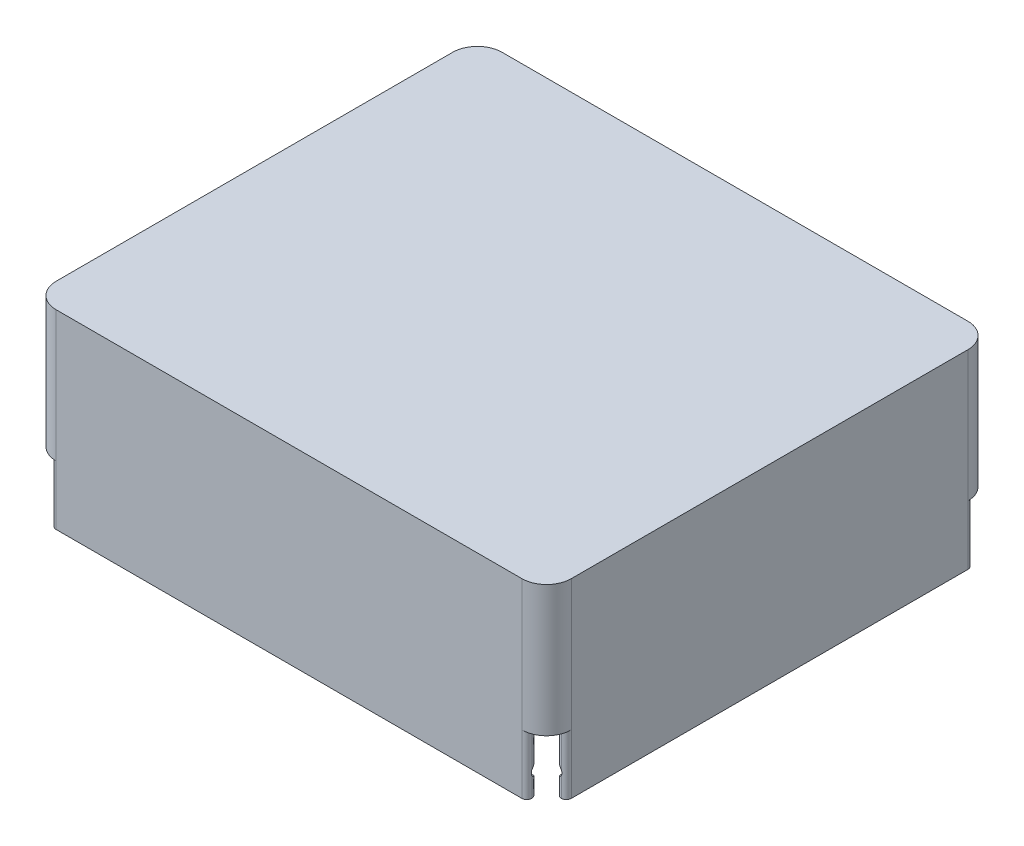
SolidWorks part; units mm, degrees
ref_plane "Plan de face" through (0, 0, 0) normal (0, 0, 1) x (1, 0, 0)
ref_plane "Plan de dessus" through (0, 0, 0) normal (0, 1, 0) x (1, 0, 0)
ref_plane "Plan de droite" through (0, 0, 0) normal (1, 0, 0) x (0, 0, -1)
sketch "Esquisse1" plane through (0, 0, 0) normal (0, 1, 0) x (1, 0, 0)
  line L1 (-52.1, -45.1) -> (52.1, -45.1)
  line L2 (-52.1, -45.1) -> (-52.1, 45.1)
  line L3 (-52.1, 45.1) -> (52.1, 45.1)
  line L4 (52.1, -45.1) -> (52.1, 45.1)
  line L5 (-52.1, -45.1) -> (52.1, 45.1) construction
  line L6 (-52.1, 45.1) -> (52.1, -45.1) construction
  point P0 (0, 0)
  dimension "D1" = 104.2
  dimension "D2" = 90.2
extrude "Boss.-Extru.1" add sketch "Esquisse1" along normal blind 2
sketch "Esquisse2" plane through (0, 0, 0) normal (0, -1, 0) x (1, 0, 0)
  line L8 (50.1, -43.1) -> (50.1, 43.1)
  line L9 (50.1, 43.1) -> (-50.1, 43.1)
  line L10 (-50.1, 43.1) -> (-50.1, -43.1)
  line L11 (-50.1, -43.1) -> (50.1, -43.1)
  line L12 (50.1, -43.1) -> (50.1, 43.1)
  line L13 (50.1, 43.1) -> (-50.1, 43.1)
  line L14 (-50.1, 43.1) -> (-50.1, -43.1)
  line L15 (-50.1, -43.1) -> (50.1, -43.1)
  line L16 (52.1, -45.1) -> (52.1, 45.1)
  line L17 (52.1, 45.1) -> (-52.1, 45.1)
  line L18 (-52.1, 45.1) -> (-52.1, -45.1)
  line L19 (-52.1, -45.1) -> (52.1, -45.1)
  line L20 (52.1, -45.1) -> (52.1, 45.1)
  line L21 (52.1, 45.1) -> (-52.1, 45.1)
  line L22 (-52.1, 45.1) -> (-52.1, -45.1)
  line L23 (-52.1, -45.1) -> (52.1, -45.1)
  dimension "D1" = 2
  dimension "D2" = 0
extrude "Boss.-Extru.2" add sketch "Esquisse2" along normal blind 36.5
sketch "Esquisse3" plane through (0, -36.5, 0) normal (0, -1, 0) x (1, 0, 0)
  line L0 (-50.1, 41.1) -> (-50.1, 43.1)
  line L1 (-52.1, 45.1) -> (-48.1, 45.1)
  line L2 (-52.1, 45.1) -> (-52.1, 41.1)
  line L3 (-52.1, 41.1) -> (-50.1, 41.1)
  line L4 (-48.1, 45.1) -> (-48.1, 43.1)
  line L5 (-50.1, 43.1) -> (-48.1, 43.1)
  dimension "D1" = 4
  dimension "D2" = 4
  dimension "D3" = 2
  dimension "D4" = 2
extrude "Enlèv. mat.-Extru.1" cut sketch "Esquisse3" against normal blind 12
mirror "Symétrie1" about plane through (0, 0, 0) normal (0, 0, 1) of "Enlèv. mat.-Extru.1"
mirror "Symétrie2" about plane through (0, 0, 0) normal (1, 0, 0) of "Symétrie1"
fillet "Congé3" radius 1 16 edges at (-48.1, -30.5, 45.1) (-48.1, -30.5, 43.1) (-50.1, -30.5, 41.1) (-52.1, -30.5, 41.1) (48.1, -30.5, 45.1) (48.1, -30.5, 43.1) (52.1, -30.5, 41.1) (50.1, -30.5, 41.1) (52.1, -30.5, -41.1) (50.1, -30.5, -41.1) (48.1, -30.5, -43.1) (48.1, -30.5, -45.1) (-48.1, -30.5, -45.1) (-48.1, -30.5, -43.1) (-50.1, -30.5, -41.1) (-52.1, -30.5, -41.1)
fillet "Congé1" radius 5 4 edges at (52.1, -11.25, 45.1) (52.1, -11.25, -45.1) (-52.1, -11.25, -45.1) (-52.1, -11.25, 45.1)
sketch "Esquisse4" plane through (0, 0, 0) normal (1, 0, 0) x (0, 0, -1)
  line L0 (-43.1, -24.5) -> (-43.1, -36.5) construction
  line L1 (-43.1, -30.9) -> (-43.1, -33.1)
  line L2 (-44.1, -36.5) -> (-43.1, -36.5) construction
  arc A1 (-43.1, -30.9) -> (-43.1, -33.1) centre (-43.1, -32) ccw
  dimension "D1" = 1.1
  dimension "D2" = 4.5
extrude "Enlèv. mat.-Extru.2" cut sketch "Esquisse4" against normal through all both and the other way through all
mirror "Symétrie4" about plane through (0, 0, 0) normal (0, 0, 1) of "Enlèv. mat.-Extru.2"
sketch "Esquisse5" plane through (0, 0, 0) normal (0, 0, 1) x (1, 0, 0)
  line L0 (-50.1, -24.5) -> (-50.1, -36.5) construction
  line L1 (-51.1, -36.5) -> (-50.1, -36.5) construction
  line L2 (-50.1, -30.9) -> (-50.1, -33.1)
  arc A0 (-50.1, -30.9) -> (-50.1, -33.1) centre (-50.1, -32) ccw
  dimension "D1" = 1.1
  dimension "D2" = 4.5
extrude "Enlèv. mat.-Extru.3" cut sketch "Esquisse5" against normal through all both and the other way through all
mirror "Symétrie5" about plane through (0, 0, 0) normal (1, 0, 0) of "Enlèv. mat.-Extru.3"
sketch "Esquisse15" plane through (0, -36.5, 0) normal (0, -1, 0) x (1, 0, 0)
  line L0 (-50.1, 40.1) -> (-50.1, -40.1) construction
  line L1 (50.3, -43.3) -> (-50.3, -43.3)
  line L2 (50.3, -43.3) -> (50.3, 43.3)
  line L3 (50.3, 43.3) -> (-50.3, 43.3)
  line L4 (-50.3, -43.3) -> (-50.3, 43.3)
  line L5 (50.3, -43.3) -> (-50.3, 43.3) construction
  line L6 (50.3, 43.3) -> (-50.3, -43.3) construction
  line L7 (47.1, 43.1) -> (-47.1, 43.1) construction
  point P0 (0, 0)
  dimension "D1" = 0.2
  dimension "D2" = 0.2
extrude "Enlèv. mat.-Extru.10" cut sketch "Esquisse15" against normal blind 4.5
sketch "Esquisse17" plane through (-52.1, 0, 0) normal (-1, 0, 0) x (0, 0, 1)
  line L0 (3.26, -41) -> (-8.74, -41) construction
  line L1 (4.26, -41) -> (-9.74, -41)
  line L2 (4.26, -41) -> (4.26, -32)
  line L3 (4.26, -32) -> (-9.74, -32)
  line L4 (-9.74, -41) -> (-9.74, -32)
  line L5 (4.26, -33) -> (4.26, -40) construction
  line L6 (-9.74, -40) -> (-9.74, -33) construction
  dimension "D1" = 9
extrude "Enlèv. mat.-Extru.11" cut sketch "Esquisse17" against normal up to surface (2 mm away) up to face at (-50.1, -19.975, 0)
fillet "Congé4" radius 1 2 edges at (-51.65, -32, 4.26) (-51.65, -32, -9.74)
